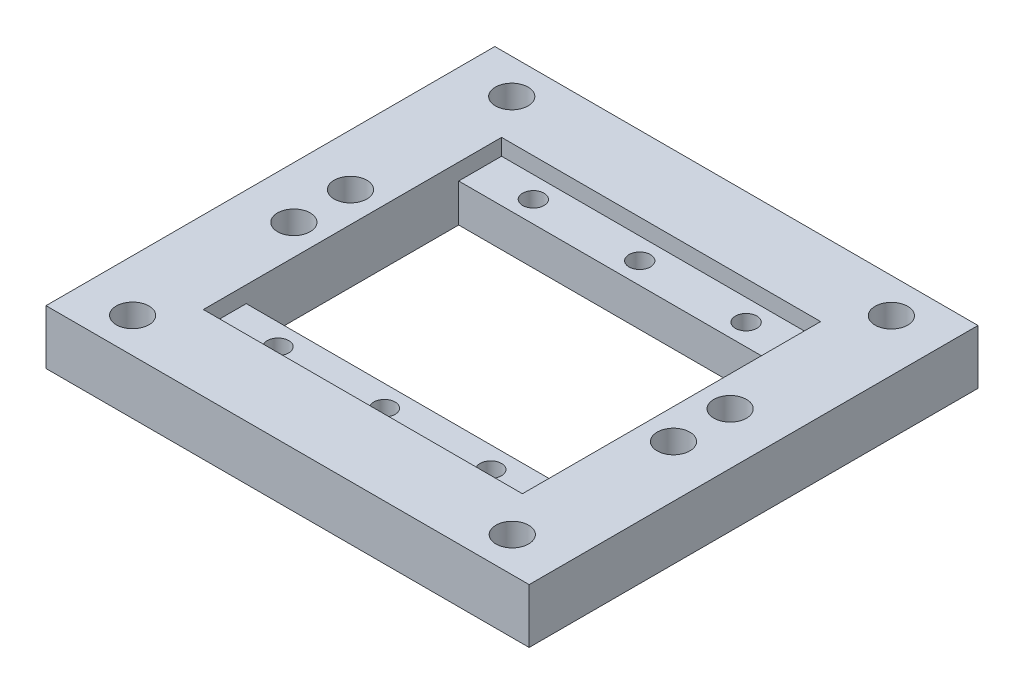
SolidWorks part; units mm, degrees
ref_plane "Front Plane" through (0, 0, 0) normal (0, 0, 1) x (1, 0, 0)
ref_plane "Top Plane" through (0, 0, 0) normal (0, 1, 0) x (1, 0, 0)
ref_plane "Right Plane" through (0, 0, 0) normal (1, 0, 0) x (0, 0, -1)
sketch "Sketch2" plane through (0, 0, 0) normal (0, 1, 0) x (1, 0, 0)
  line L1 (0, 0) -> (112.649, 0)
  line L2 (0, 0) -> (0, 104.648)
  line L3 (0, 104.648) -> (112.649, 104.648)
  line L4 (112.649, 0) -> (112.649, 104.648)
  line L5 (19.13, 27.559) -> (93.519, 27.559)
  line L6 (19.13, 27.559) -> (19.13, 77.089)
  line L7 (19.13, 77.089) -> (93.519, 77.089)
  line L8 (93.519, 27.559) -> (93.519, 77.089)
  line L9 (19.13, 87.089) -> (93.519, 87.089)
  line L10 (19.13, 87.089) -> (19.13, 17.559)
  line L11 (19.13, 17.559) -> (93.519, 17.559)
  line L12 (93.519, 87.089) -> (93.519, 17.559)
  circle A0 centre (12.065, 96.52) radius 3.81
  circle A1 centre (12.065, 58.928) radius 3.81
  circle A2 centre (12.065, 45.72) radius 3.81
  circle A3 centre (12.065, 8.128) radius 3.81
  circle A4 centre (100.584, 8.128) radius 3.81
  circle A5 centre (100.584, 45.72) radius 3.81
  circle A6 centre (100.584, 58.928) radius 3.81
  circle A7 centre (100.584, 96.52) radius 3.81
  circle A8 centre (31.5337, 82.089) radius 2.5
  circle A9 centre (56.341, 82.089) radius 2.5
  circle A10 centre (81.1483, 82.089) radius 2.5
  circle A11 centre (81.1483, 22.559) radius 2.5
  circle A12 centre (56.341, 22.559) radius 2.5
  circle A13 centre (31.5337, 22.559) radius 2.5
  dimension "D11" = 5
  dimension "D12" = 7.62
  dimension "D20" = 37.592
  dimension "D1" = 104.648
  dimension "D2" = 112.649
  dimension "D5" = 27.559
  dimension "D6" = 27.559
  dimension "D7" = 10
  dimension "D8" = 10
  dimension "D9" = 19.13
  dimension "D10" = 19.13
  dimension "D13" = 12.065
  dimension "D14" = 12.065
  dimension "D15" = 12.4037
  dimension "D16" = 24.8073
  dimension "D17" = 24.8073
  dimension "D18" = 5
  dimension "D19" = 5
  dimension "D21" = 37.592
  dimension "D22" = 8.128
  dimension "D23" = 8.128
extrude "Boss-Extrude5" add sketch "Sketch2" along normal blind 12.7 contours L1 L4 L3 L2 L9 L12 L11 L10 region at (1.5376, 0, -52.324)
extrude "Boss-Extrude7" add sketch "Sketch2<4>" along normal blind 8.89 contours L12 L9 L10 L7 A10 A9 A8 | L12 L5 L10 L11 A13 A12 A11 region at (56.3245, 0, -26.8084) region at (19.8806, 0, -82.089)
sketch "Sketch2<4>" plane through (0, 0, 0) normal (0, 1, 0) x (1, 0, 0) same geometry as "Sketch2"
